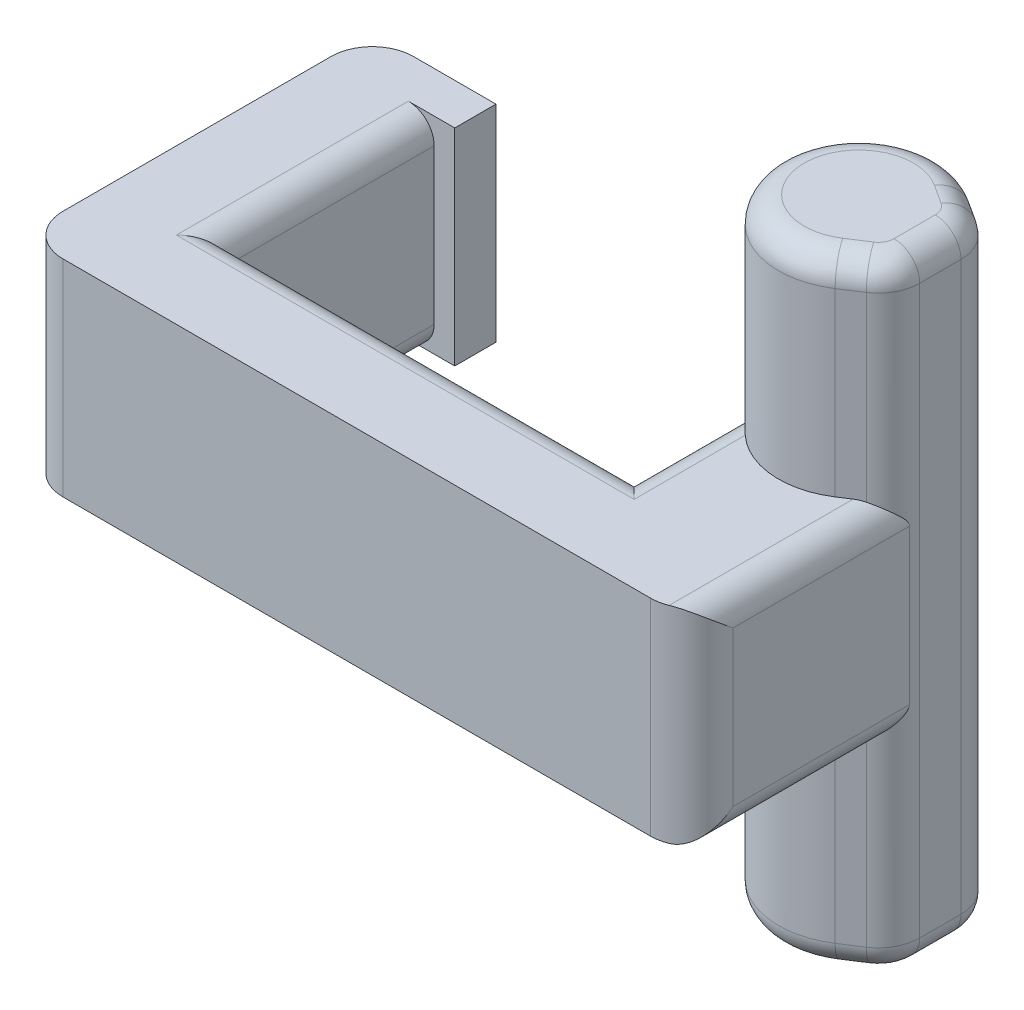
SolidWorks part; units mm, degrees
ref_plane "Front Plane" through (0, 0, 0) normal (1, 0, 0) x (0, 1, 0)
ref_plane "Top Plane" through (0, 0, 0) normal (0, 0, 1) x (0, 1, 0)
ref_plane "Right Plane" through (0, 0, 0) normal (0, 1, 0) x (-1, 0, 0)
sketch "Sketch1" plane through (0, 0, 0) normal (0, 1, 0) x (-1, 0, 0)
  circle A0 centre (0, 0) radius 4.953
  dimension "D1" = 9.906
extrude "Boss-Extrude1" add sketch "Sketch1" along normal mid plane 38.1
sketch "Sketch3" plane through (0, 0, 0) normal (0, 1, 0) x (-1, 0, 0)
  line L0 (-4.953, 0) -> (-4.953, 15.24)
  line L1 (-4.953, 15.24) -> (36.322, 15.24)
  line L2 (36.322, 15.24) -> (36.322, -6.35)
  line L3 (36.322, -6.35) -> (28.702, -6.35)
  line L4 (28.702, -6.35) -> (28.702, -3.81)
  line L5 (28.702, -3.81) -> (29.972, -3.81)
  line L6 (29.972, -3.81) -> (29.972, 8.89)
  line L7 (29.972, 8.89) -> (4.953, 8.89)
  line L8 (4.953, 8.89) -> (4.953, 0)
  line L9 (-4.953, 0) -> (-4.953, -6.35) construction
  line L10 (-4.953, -6.35) -> (28.702, -6.35) construction
  line L11 (29.972, 15.24) -> (29.972, 8.89) construction
  line L12 (36.322, 8.89) -> (29.972, 8.89) construction
  line L13 (-4.953, 0) -> (4.953, 0) construction
  line L14 (-4.953, -6.35) -> (-8.763, -6.35) construction
  line L15 (-8.763, -6.35) -> (-8.763, 15.24) construction
  line L16 (-8.763, 15.24) -> (-4.953, 15.24) construction
  line L17 (0, 4.953) -> (4.953, 4.953) construction
  circle A0 centre (0, 0) radius 4.953 construction
  circle A2 centre (0, 0) radius 4.953
  arc A3 (-4.953, 0) -> (4.953, 0) centre (0, 0) ccw
  dimension "D1" = 3.937
  dimension "D2" = 2.54
  dimension "D3" = 1.27
  dimension "D4" = 90
  dimension "D5" = 6.35
  dimension "D7" = 45.085
  dimension "D8" = 3.81
  dimension "D9" = 6.35
  dimension "D6" = 0
extrude "Boss-Extrude2" add sketch "Sketch3" along normal mid plane 12.7
fillet "Fillet1" radius 2.54 3 edges at (-36.322, 0, -6.35) (-36.322, 0, 15.24) (4.953, 0, 15.24)
sketch "Sketch4" plane through (0, -19.05, 0) normal (0, -1, 0) x (1, 0, 0)
  line L0 (5.0165, 1.27) -> (5.0165, -1.27)
  line L1 (3.8585, -3.4011) -> (2.6949, -4.1557)
  line L2 (3.8585, 3.4011) -> (2.6949, 4.1557)
  line L3 (0, 0) -> (5.0165, 0) construction
  line L4 (2.6949, 4.1557) -> (2.6949, -4.1557)
  arc A0 (4.953, 0) -> (-4.953, 0) centre (0, 0) ccw construction
  circle A1 centre (0, 0) radius 4.953 construction
  arc A2 (3.8585, -3.4011) -> (5.0165, -1.27) centre (2.4765, -1.27) ccw
  arc A3 (5.0165, 1.27) -> (3.8585, 3.4011) centre (2.4765, 1.27) ccw
  dimension "D1" = 2.54
  dimension "D2" = 2.54
  dimension "D3" = 5.0165
extrude "Boss-Extrude3" add sketch "Sketch4" against normal up to surface (38.1 mm away) up to face at (0, 19.05, 4.953)
fillet "Fillet2" radius 1.5875 18 edges at (3.2767, -19.05, -3.7784) (4.7083, -19.05, -2.4827) (5.0165, -19.05, 0) (4.7083, -19.05, 2.4827) (3.2767, -19.05, 3.7784) (3.2767, 19.05, -3.7784) (4.7083, 19.05, -2.4827) (5.0165, 19.05, 0) (4.7083, 19.05, 2.4827) (3.2767, 19.05, 3.7784) (-4.953, 19.05, 0) (-4.953, -19.05, 0) (-4.953, 6.35, 4.445) (-4.953, -6.35, 4.445) (-29.972, 6.35, 2.54) (-29.972, -6.35, 2.54) (-17.4625, 6.35, 8.89) (-17.4625, -6.35, 8.89)
fillet "Fillet3" radius 1.5875 2 edges at (4.953, -6.35, 7.2672) (4.953, 6.35, 7.2672)
